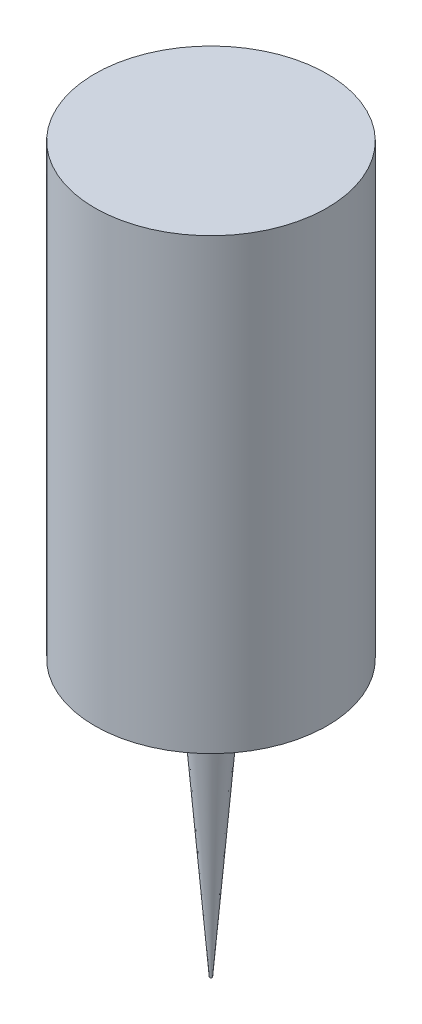
SolidWorks part; units mm, degrees
ref_plane "Front Plane" through (0, 0, 0) normal (0, 0, 1) x (1, 0, 0)
ref_plane "Top Plane" through (0, 0, 0) normal (0, 1, 0) x (1, 0, 0)
ref_plane "Right Plane" through (0, 0, 0) normal (1, 0, 0) x (0, 0, -1)
sketch "Sketch1" plane through (0, 0, 0) normal (0, 1, 0) x (1, 0, 0)
  circle A0 centre (0, 0) radius 2.54
  dimension "D1" = 5.08
extrude "Boss-Extrude1" add sketch "Sketch1" along normal blind 9.8044
ref_axis "Axis1" through (0, 9.8044, 0) along (0, -1, 0)
sketch "Sketch2" plane through (0, 0, 0) normal (0, 0, 1) x (1, 0, 0)
  line L0 (0, 0) -> (0, -6.35)
  line L1 (0, -6.35) -> (-0.508, 0)
  line L2 (-0.508, 0) -> (0, 0)
  line L3 (-2.54, 0) -> (2.54, 0) construction
  arc A0 (-0.0261, -6.0242) -> (0, -6.0332) centre (0, -5.9911) ccw
  point P9 (0, -5.8619)
  point P10 (0, -5.9041)
  point P11 (0, -5.9911)
  dimension "D1" = 0.508
  dimension "D2" = 6.35
revolve "Revolve1" add sketch "Sketch2" angle 360 about L0 region at (-0.1697, -2.1065, 0)
